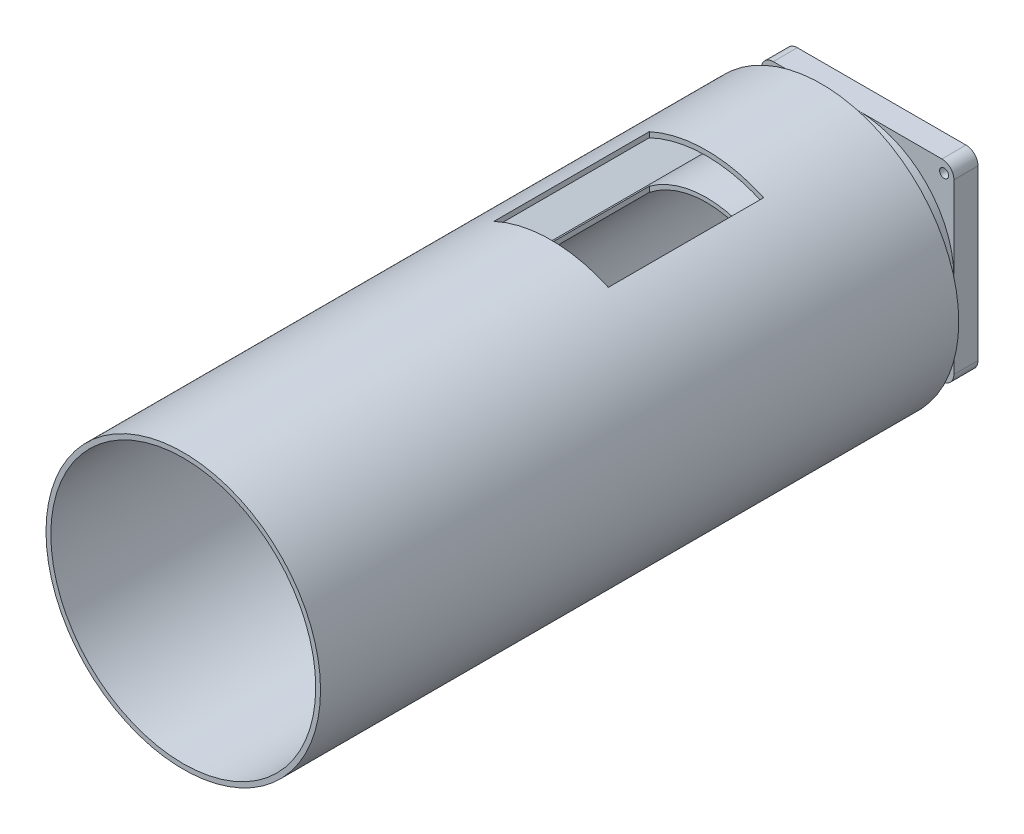
SolidWorks part; units mm, degrees
note: '?' marks a value the reader was unsure of.
ref_plane "前视基准面" through (0, 0, 0) normal (0, 0, 1) x (1, 0, 0)
ref_plane "上视基准面" through (0, 0, 0) normal (0, 1, 0) x (1, 0, 0)
ref_plane "右视基准面" through (0, 0, 0) normal (1, 0, 0) x (0, 0, -1)
ref_axis "基准轴1" through (0, 0, 20.9) along (0, 0, -1)?
ref_plane "基准面1" through (55, 0, 0) normal (1, 0, 0) x (0, 0, -1)
sketch "草图7" plane through (0, 0, 0) normal (0, 0, 1) x (1, 0, 0)
  line L1 (-40, 40) -> (40, 40)
  line L2 (-40, 40) -> (-40, -40)
  line L3 (-40, -40) -> (40, -40)
  line L4 (40, 40) -> (40, -40)
  line L5 (-40, 40) -> (40, -40) construction
  line L6 (-40, -40) -> (40, 40) construction
  circle A0 centre (0, 0) radius 50.7986 construction
  circle A1 centre (-35.92, 35.92) radius 1.875
  circle A2 centre (35.92, 35.92) radius 1.875
  circle A3 centre (35.92, -35.92) radius 1.875
  circle A4 centre (-35.92, -35.92) radius 1.875
  circle A5 centre (0, 0) radius 38.25
  point P0 (0, 0)
  point P17 (0, 38.25)
  dimension "D2" = 3.75
  dimension "D4" = 76.5
  dimension "D1" = 80
  dimension "D3" = 71.84
extrude "凸台-拉伸3" [suppressed] add sketch "草图7" along normal mid plane 25 contours A5 | L4 L1 L2 L3 A5 A4 A3 A2 A1
fillet "圆角1" [suppressed] radius 5
sketch "草图2" [suppressed] plane through (0, 0, 0) normal (0, 1, 0) x (1, 0, 0)
  line L0 (0, 12.5) -> (0, -12.5) construction
  line L1 (0, 0) -> (89.5, 0) construction
  line L3 (89.5, -8.5) -> (39.5, -8.5)
  line L4 (89.5, -8.5) -> (89.5, 8.5)
  line L5 (89.5, 8.5) -> (39.5, 8.5)
  line L6 (39.5, -8.5) -> (39.5, 8.5)
  line L7 (38.25, 4.5) -> (17.5, 4.5)
  line L8 (38.25, 4.5) -> (38.25, -12.5)
  line L9 (38.25, -12.5) -> (14.5, -12.5)
  line L10 (14.5, -12.5) -> (0, -12.5)
  line L12 (17.5, 4.5) -> (17.5, -9.5)
  line L14 (-40, 12.5) -> (40, 12.5) construction
  arc A2 (14.5, -12.5) -> (17.5, -9.5) centre (14.5, -9.5) ccw
  point P14 (38.25, 0)
  dimension "D8" = 3
  dimension "D1" = 4
  dimension "D2" = 79
  dimension "D3" = 50
  dimension "D4" = 8
  dimension "D6" = 35
revolve "切除-旋转1" [suppressed] cut sketch "草图2" angle 360 about L0
sketch "草图3" [suppressed] plane through (0, 0, 0) normal (0, 0, 1) x (1, 0, 0)
  line L0 (0, 0) -> (0, 17.5) construction
  line L1 (8.0065, 15.561) -> (38.25, 0)
  line L3 (9.473, -14.7144) -> (-19.125, -33.1255)
  line L4 (-17.4795, -0.8466) -> (-19.125, 33.1255)
  line L5 (37.8635, -5.4241) -> (16.6094, 5.5116)
  circle A0 centre (0, 0) radius 17.5
  arc A1 (-19.125, -33.1255) -> (38.25, 0) centre (0, 0) ccw
  circle A2 centre (0, 0) radius 38.25 construction
  point P17 (0, 0)
  dimension "D2" = 5
  dimension "D1" = 3
extrude "切除-拉伸1" [suppressed] cut sketch "草图3" against normal through all contours L3 A1 L5 A0
pattern_circular "阵列(圆周)1" [suppressed] count 3 over 360 about axis through (0, 0, 20.9) along (0, 0, -1)
sketch "草图4" plane through (0, 0, 0) normal (1, 0, 0) x (0, 0, -1)
  line L0 (-14.3137, 11.3137) -> (8.3137, -11.3137) construction
  line L1 (-13.4298, 12.1976) -> (9.1976, -10.4298)
  line L2 (-15.1976, 10.4298) -> (7.4298, -12.1976)
  line L3 (-20.9, 0) -> (20.9, 0) construction
  arc A0 (-13.4298, 12.1976) -> (-15.1976, 10.4298) centre (-14.3137, 11.3137) ccw
  arc A1 (7.4298, -12.1976) -> (9.1976, -10.4298) centre (8.3137, -11.3137) ccw
  point P2 (-3, 0)
  dimension "D1" = 2.5
  dimension "D2" = 45
  dimension "D3" = 32
  dimension "D4" = 3
sketch "草图5" plane through (55, 0, 0) normal (1, 0, 0) x (0, 0, -1)
  line L0 (-11.8163, 50) -> (5.8163, -50) construction
  line L1 (-10.5853, 50.2171) -> (7.0474, -49.7829)
  line L2 (-13.0474, 49.7829) -> (4.5853, -50.2171)
  line L3 (-20.9, 0) -> (20.9, 0) construction
  arc A0 (-10.5853, 50.2171) -> (-13.0474, 49.7829) centre (-11.8163, 50) ccw
  arc A1 (4.5853, -50.2171) -> (7.0474, -49.7829) centre (5.8163, -50) ccw
  arc A2 (-13.4298, 12.1976) -> (-15.1976, 10.4298) centre (-14.3137, 11.3137) ccw construction
  point P2 (-3, 0)
  dimension "D1" = 80
  dimension "D2" = 100
loft "放样1" [suppressed] add profiles "草图4", "草图5"
sketch "草图6" [suppressed] plane through (0, 0, 0) normal (0, 0, 1) x (1, 0, 0)
  line L0 (0, 11.3137) -> (0, -11.3137) construction
  line L1 (0, 0) -> (19.8943, -19.8943)
  line L2 (0, 0) -> (19.3185, 5.1764)
  line L3 (0, -65.4206) -> (0, 62.9965) construction
  line L5 (0, 0) -> (112.9869, 0) construction
  arc A0 (37.2417, -0.7851) -> (32.5394, -18.1314) centre (0, 0) cw
  arc A1 (32.466, 1.6957) -> (19.3185, 5.1764) centre (27.2947, 8.7333) cw
  arc A2 (32.5394, -18.1314) -> (19.8943, -19.8943) centre (25.5511, -14.2374) cw
  arc A3 (37.2417, -0.7851) -> (32.466, 1.6957) centre (34.2424, -0.7219) ccw
  circle A4 centre (0, 0) radius 38.25 construction
  point P17 (35.9807, 9.641)
  dimension "D1" = 60
  dimension "D3" = 8
  dimension "D4" = 1
  dimension "D6" = 3
  dimension "D2" = 45
  dimension "D5" = 20
extrude "切除-拉伸2" [suppressed] cut sketch "草图6" against normal mid plane 100 flip side to cut contours A0 A3 A1 L2 L1 A2
pattern_circular "阵列(圆周)3" [suppressed] count 5 over 360 about axis through (0, 0, 20.9) along (0, 0, -1)
fillet "圆角2" [suppressed] radius 3
sketch "Sketch1" plane through (0, 0, 0) normal (0, 0, 1) x (1, 0, 0)
  line L0 (0, -40) -> (0, 40) construction
  line L1 (-40, 0) -> (40, 0) construction
  line L8 (35, 40) -> (-35, 40)
  line L9 (-40, 35.0014) -> (-40, -34.9986)
  line L10 (-35, -40) -> (35, -40)
  line L11 (40, -34.9986) -> (40, 35.0014)
  arc A9 (-35, 40) -> (-40, 35.0014) centre (-35, 35) ccw
  arc A10 (-40, -34.9986) -> (-35, -40) centre (-35, -35) ccw
  arc A11 (35, -40) -> (40, -34.9986) centre (35, -35) ccw
  arc A12 (40, 35.0014) -> (35, 40) centre (35, 35) ccw
  circle A13 centre (-35.92, 35.336) radius 1.875
  circle A14 centre (-35.92, -35.92) radius 1.875
  circle A15 centre (35.92, 35.336) radius 1.875
  circle A16 centre (35.92, -35.92) radius 1.875
  circle A17 centre (0, 0) radius 38.25
  point P16 (0, 0)
  point P30 (0, 0)
  dimension "D2" = 5
  dimension "D3" = 3.75
  dimension "D6" = 76.5
  dimension "D10" = 5
  dimension "D1" = 70
  dimension "D4" = 40
  dimension "D5" = 50.7986
  dimension "D7" = 40
  dimension "D8" = 1.3011
  dimension "D9" = 35.336
extrude "Boss-Extrude1" add sketch "Sketch1" along normal mid plane 10 separate body
sketch "Sketch2" plane through (0, 0, 5) normal (0, 0, 1) x (1, 0, 0)
  circle A0 centre (0, 0) radius 40
  circle A1 centre (0, 0) radius 38.25 construction
  circle A2 centre (0, 0) radius 38.25
  dimension "D1" = 80
extrude "Boss-Extrude2" add sketch "Sketch2" along normal blind 200 separate body
ref_plane "Plane1" through (0, 0, 20) normal (0, 0, 1) x (1, 0, 0)
sketch "Sketch3" plane through (0, 0, 20) normal (0, 0, 1) x (1, 0, 0)
  line L0 (0, -38.25) -> (0, -55) construction
  line L1 (-1.75, -38.2099) -> (-1.75, -54.9722)
  line L2 (1.75, -38.2099) -> (1.75, -54.9722)
  line L3 (-33.1255, 19.125) -> (-47.6314, 27.5) construction
  line L4 (-32.2158, 20.6205) -> (-46.7323, 29.0016)
  line L5 (-33.9658, 17.5894) -> (-48.4823, 25.9705)
  line L6 (33.1255, 19.125) -> (47.6314, 27.5) construction
  line L7 (33.9658, 17.5894) -> (48.4823, 25.9705)
  line L8 (32.2158, 20.6205) -> (46.7323, 29.0016)
  circle A0 centre (0, 0) radius 55
  circle A1 centre (0, 0) radius 57
  circle A2 centre (0, 0) radius 38.25 construction
  circle A3 centre (0, 0) radius 38.25
  dimension "D1" = 110
  dimension "D3" = 1.75
  dimension "D2" = 2
  dimension "D4" = 3
extrude "Boss-Extrude3" add sketch "Sketch3" along normal through all separate body contours A1 A0 | A3 L1 A0 L2 | A3 L4 A0 L5 | A3 L7 A0 L8
sketch "Sketch4" plane through (0, 0, 0) normal (0, 1, 0) x (1, 0, 0)
  line L0 (-57, -205) -> (57, -205) construction
  line L1 (57, -20) -> (-57, -20) construction
  line L2 (-57, -205) -> (57, -205)
  line L3 (57, -20) -> (-57, -20)
  line L4 (0, 5) -> (0, -205) construction
  line L6 (-23.75, -67.75) -> (23.75, -67.75)
  line L7 (-23.75, -67.75) -> (-23.75, -132.25)
  line L8 (-23.75, -132.25) -> (23.75, -132.25)
  line L9 (23.75, -67.75) -> (23.75, -132.25)
  line L10 (-23.75, -67.75) -> (23.75, -132.25) construction
  line L11 (-23.75, -132.25) -> (23.75, -67.75) construction
  line L13 (35, 5) -> (-35, 5) construction
  line L14 (35, 5) -> (-35, 5)
  point P4 (0, -100)
  point P7 (0, -100)
  point P20 (0, 5)
  dimension "D1" = 47.5
  dimension "D2" = 64.5
extrude "Cut-Extrude1" cut sketch "Sketch4" along normal through all contours L9 L6 L7 L8
ref_plane "Plane2" through (0, 0, 132.25) normal (0, 0, -1) x (-1, 0, 0)
sketch "Sketch5" plane through (0, 0, 132.25) normal (0, 0, -1) x (-1, 0, 0)
  line L0 (-23.75, 32.186) -> (-23.75, 29.9833) construction
  line L1 (23.75, 29.9833) -> (23.75, 32.186) construction
  line L2 (23.75, 49.6078) -> (23.75, 51.8164) construction
  line L3 (-23.75, 51.8164) -> (-23.75, 49.6078) construction
  line L4 (-23.75, 32.186) -> (-23.75, 29.9833)
  line L5 (23.75, 29.9833) -> (23.75, 32.186)
  line L6 (23.75, 49.6078) -> (23.75, 51.8164)
  line L7 (-23.75, 51.8164) -> (-23.75, 49.6078)
  line L8 (-23.75, 49.6078) -> (-23.75, 32.186)
  line L9 (23.75, 49.6078) -> (23.75, 32.186)
  arc A0 (23.75, 32.186) -> (-23.75, 32.186) centre (0, 0) ccw construction
  arc A1 (23.75, 29.9833) -> (-23.75, 29.9833) centre (0, 0) ccw construction
  arc A2 (23.75, 51.8164) -> (-23.75, 51.8164) centre (0, 0) ccw construction
  arc A3 (23.75, 49.6078) -> (-23.75, 49.6078) centre (0, 0) ccw construction
  arc A4 (23.75, 32.186) -> (-23.75, 32.186) centre (0, 0) ccw
  arc A5 (23.75, 29.9833) -> (-23.75, 29.9833) centre (0, 0) ccw
  arc A6 (23.75, 51.8164) -> (-23.75, 51.8164) centre (0, 0) ccw
  arc A7 (23.75, 49.6078) -> (-23.75, 49.6078) centre (0, 0) ccw
extrude "Boss-Extrude4" add sketch "Sketch5" against normal blind 2 contours L9 A7 L8 A4
sketch "Sketch6" plane through (0, 0, 205) normal (0, 0, 1) x (1, 0, 0)
  circle A0 centre (0, 0) radius 57 construction
  circle A1 centre (0, 0) radius 57
  circle A2 centre (0, 0) radius 55
  arc M6 (-46.7323, 29.0016) -> (46.7323, 29.0016) centre (0, 0) cw
  arc M10 (-1.75, -54.9722) -> (-48.4823, 25.9705) centre (0, 0) cw
  arc M14 (48.4823, 25.9705) -> (1.75, -54.9722) centre (0, 0) cw
  circle M16 centre (0, 0) radius 57
extrude "Boss-Extrude5" add sketch "Sketch6" along normal blind 80 contours A2 M16 M14 M10 M6 | A1
ref_plane "Plane3" through (0, 0, 100) normal (0, 0, -1) x (-1, 0, 0)
